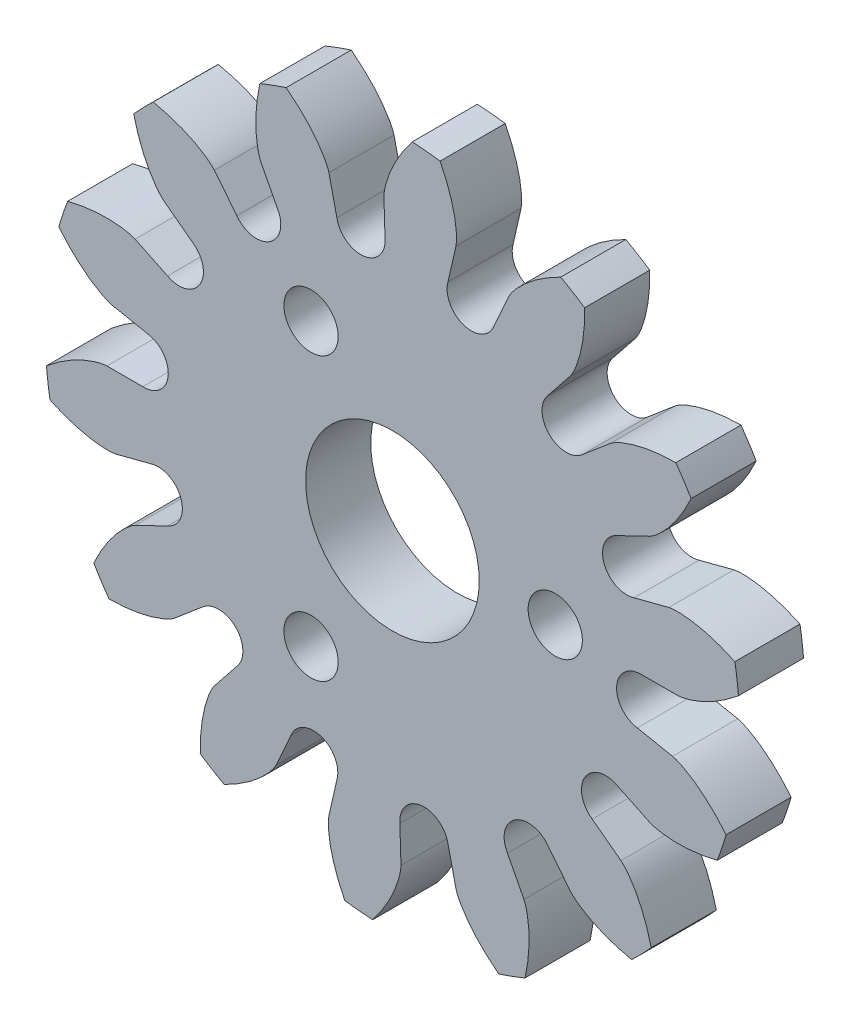
SolidWorks part; units mm, degrees
material "A2017"
ref_plane "正面" through (0, 0, 0) normal (0, 0, 1) x (1, 0, 0)
ref_plane "平面" through (0, 0, 0) normal (0, 1, 0) x (1, 0, 0)
ref_plane "右側面" through (0, 0, 0) normal (1, 0, 0) x (0, 0, -1)
sketch "歯車作図" plane through (0, 0, 0) normal (0, 0, 1) x (1, 0, 0)
  line L0 (0, 0) -> (11.5, 0) construction
  line L1 (11.5, 0) -> (13.1557, 0)
  line L2 (0, 0) -> (15.9243, -1.5543)
  circle A0 centre (0, 0) radius 16
  circle A1 centre (0, 0) radius 14 construction
  circle A2 centre (0, 0) radius 13.1557 construction
  circle A3 centre (0, 0) radius 11.5 construction
  arc A4 (13.9338, -1.36) -> (13.9984, 0.2086) centre (0, 0) ccw
  spline S0 degree 4 poles (13.1557, 0) (13.1962, 0.0018) (13.3095, 0.0121) (13.5229, 0.0532) (13.8623, 0.15) (14.2878, 0.3185) (14.8127, 0.5835) (15.3953, 0.9517) (15.9956, 1.4129) (16.5963, 1.9652) (17.1516, 2.5628) (17.6623, 3.1989) (18.1526, 3.9005) (18.7007, 4.8078) (19.264, 5.9401) (19.7932, 7.3107) (20.2281, 8.8843) (20.5168, 10.4909) (20.6662, 12.1159) (20.6828, 13.7479) (20.5733, 15.3756) (20.3435, 16.9914) (20.0435, 18.386) (19.7179, 19.5668) (19.4366, 20.4368) (19.2304, 21.0178) (19.0543, 21.4853) (18.8956, 21.8825) (18.7682, 22.1927) (18.6164, 22.5421) (18.4593, 22.8947) (18.2968, 23.2444) (18.0021, 23.8548) (17.7431, 24.3427) (17.4714, 24.849) (17.3291, 25.0891) (17.2373, 25.2512) knots 0 0 0 0 0 0.005604 0.015718 0.02996 0.048734 0.068727 0.096889 0.125051 0.153212 0.181374 0.209535 0.237696 0.271429 0.327752 0.384075 0.440398 0.496721 0.553044 0.609367 0.66569 0.722013 0.778336 0.806497 0.834659 0.84874 0.86282 0.876901 0.890982 0.900036 0.909091 0.931818 0.954545 0.977273 1 1 1 1 1 construction
  spline S1 degree 4 poles (13.1557, 0) (13.1962, 0.0018) (13.3095, 0.0121) (13.5229, 0.0532) (13.8623, 0.15) (14.2878, 0.3185) (14.8127, 0.5835) (15.3953, 0.9517) (15.9956, 1.4129) (16.5963, 1.9652) (17.1516, 2.5628) (17.6623, 3.1989) (18.1526, 3.9005) (18.7007, 4.8078) (19.264, 5.9401) (19.7932, 7.3107) (20.2281, 8.8843) (20.5168, 10.4909) (20.6662, 12.1159) (20.6828, 13.7479) (20.5733, 15.3756) (20.3435, 16.9914) (20.0435, 18.386) (19.7179, 19.5668) (19.4366, 20.4368) (19.2304, 21.0178) (19.0543, 21.4853) (18.8956, 21.8825) (18.7682, 22.1927) (18.6164, 22.5421) (18.5243, 22.7488) (18.475, 22.8577) (18.4502, 22.9118) knots 0 0 0 0 0 0.005604 0.015718 0.02996 0.048734 0.068727 0.096889 0.125051 0.153212 0.181374 0.209535 0.237696 0.271429 0.327752 0.384075 0.440398 0.496721 0.553044 0.609367 0.66569 0.722013 0.778336 0.806497 0.834659 0.84874 0.86282 0.876901 0.890982 0.900036 0.909091 0.909091 0.909091 0.909091 0.909091
  dimension "歯先円直径" = 32
  dimension "基礎ピッチ円直径" = 28
  dimension "基礎円直径" = 26.3114
  dimension "全歯丈" = 4.5
  dimension "基準ピッチ" = 1.5708
sketch "ｽｹｯﾁ1" plane through (0, 0, 0) normal (0, 0, 1) x (1, 0, 0)
  circle A0 centre (0, 0) radius 16 construction
  circle A1 centre (0, 0) radius 16
extrude "ﾎﾞｽ - 押し出し1" add sketch "ｽｹｯﾁ1" along normal mid plane 3
sketch "ｽｹｯﾁ3" plane through (0, 0, 1.5) normal (0, 0, 1) x (1, 0, 0)
  line L0 (11.5, 0) -> (13.1557, 0) construction
  line L1 (0, 0) -> (15.9243, -1.5543) construction
  line L2 (11.5, 0) -> (13.1557, 0)
  line L3 (11.4456, -1.1172) -> (15.9243, -1.5543)
  arc A0 (11.4456, -1.1172) -> (11.5, 0) centre (0, 0) ccw
  circle A1 centre (0, 0) radius 16
  arc A2 (15.9243, -1.5543) -> (15.9399, 1.3859) centre (0, 0) ccw
  spline S0 degree 4 poles (3.878, 2999.7691) (4.1335, 73.9467) (7.9689, 1.3767) (11.1984, -0.6096) (13.8623, 0.15) (14.2878, 0.3185) (14.8127, 0.5835) (15.3953, 0.9517) (15.9956, 1.4129) (16.5963, 1.9652) (17.1516, 2.5628) (17.6623, 3.1989) (18.1526, 3.9005) (18.7007, 4.8078) (19.264, 5.9401) (19.7932, 7.3107) (20.2281, 8.8843) (20.5168, 10.4909) (20.6662, 12.1159) (20.6828, 13.7479) (20.5733, 15.3756) (20.3435, 16.9914) (20.0435, 18.386) (19.7179, 19.5668) (19.4366, 20.4368) (19.2304, 21.0178) (19.0543, 21.4853) (18.8956, 21.8825) (18.7682, 22.1927) (17.4635, 25.1948) (18.1341, 22.9305) (4.6054, 50.9334) (-1231.5015, 2749.6934) knots -0.333742 -0.333742 -0.333742 -0.333742 -0.333742 0.005604 0.015718 0.02996 0.048734 0.068727 0.096889 0.125051 0.153212 0.181374 0.209535 0.237696 0.271429 0.327752 0.384075 0.440398 0.496721 0.553044 0.609367 0.66569 0.722013 0.778336 0.806497 0.834659 0.84874 0.86282 0.876901 0.890982 0.900036 1.260415 1.260415 1.260415 1.260415 1.260415 only from (13.1557, 0) to (18.4502, 22.9118) construction
  spline S1 degree 4 poles (13.1557, 0) (13.1962, 0.0018) (13.3095, 0.0121) (13.5229, 0.0532) (13.8623, 0.15) (14.2878, 0.3185) (14.8127, 0.5835) (15.2963, 0.8892) (15.6468, 1.1478) (15.873, 1.3305) (15.9399, 1.3859) knots 0 0 0 0 0 0.005604 0.015718 0.02996 0.048734 0.068727 0.096889 0.108898 0.108898 0.108898 0.108898 0.108898
  dimension "D1" = 0
extrude "ｶｯﾄ - 押し出し1" cut sketch "ｽｹｯﾁ3" against normal through all
pattern_circular "円形ﾊﾟﾀｰﾝ4" count 14 over 360 about axis through (0, 0, 1.5) along (0, 0, -1) of "ｶｯﾄ - 押し出し1"
mirror "ﾐﾗｰ1" about plane through (11.4456, -1.1172, -1.5) normal (-0.0971, -0.9953, 0) of "円形ﾊﾟﾀｰﾝ4", "ｶｯﾄ - 押し出し1"
sketch "ｽｹｯﾁ5" plane through (0, 0, 1.5) normal (0, 0, 1) x (1, 0, 0)
  circle A0 centre (0, 0) radius 4
  dimension "D1" = 8
extrude "ｶｯﾄ - 押し出し3" cut sketch "ｽｹｯﾁ5" against normal through all
hole_wizard "M3 ねじ穴1" positions "ｽｹｯﾁ6" profile "ｽｹｯﾁ7" tap size "M3" standard "JIS" end condition through all
sketch "ｽｹｯﾁ6" plane through (0, 0, 1.5) normal (0, 0, 1) x (1, 0, 0)
  line L0 (7.5, 0) -> (0, 0) construction
  circle A0 centre (0, 0) radius 7.5
  point P0 (7.5, 0)
  dimension "D1" = 15
sketch "ｽｹｯﾁ7" plane through (7.5, 0, 1.5) normal (1, 0, 0) x (0, -1, 0)
  line L0 (0, 0) -> (0, 3)
  line L1 (0, 3) -> (1.25, 3)
  line L2 (1.25, 3) -> (1.25, 0)
  line L5 (1.25, 0) -> (0, 0)
  line L11 (0, -6.35) -> (0, 107.95) construction
  dimension "次ｻｰﾌｪｽまでのねじ下穴ﾄﾞﾘﾙ直径" = 2.5
  dimension "次ｻｰﾌｪｽまでのねじ下穴ﾄﾞﾘﾙの深さ" = 3
cosmetic thread "穴のねじ山1" parameters "D2"=3
pattern_circular "円形ﾊﾟﾀｰﾝ6" count 3 over 360 about axis through (0, 0, -1.5) along (0, 0, 1) of "M3 ねじ穴1"
sketch "ｽｹｯﾁ8" plane through (0, 0, 1.5) normal (0, 0, 1) x (1, 0, 0)
  circle A0 centre (3.6361, 10.91) radius 1.1185
  arc A1 (4.6787, 10.5052) -> (2.559, 11.2117) centre (0, 0) ccw construction
  circle A2 centre (8.0097, 8.252) radius 1.1185
  circle A3 centre (10.7969, 3.9595) radius 1.1185
  circle A4 centre (11.4456, -1.1172) radius 1.1185
  circle A5 centre (9.8274, -5.9726) radius 1.1185
  circle A6 centre (6.2628, -9.6451) radius 1.1185
  circle A7 centre (1.4577, -11.4072) radius 1.1185
  circle A8 centre (-3.6361, -10.91) radius 1.1185
  circle A9 centre (-8.0097, -8.252) radius 1.1185
  circle A10 centre (-10.7969, -3.9595) radius 1.1185
  circle A11 centre (-11.4456, 1.1172) radius 1.1185
  circle A12 centre (-9.8274, 5.9726) radius 1.1185
  circle A13 centre (-6.2628, 9.6451) radius 1.1185
  circle A14 centre (-1.4577, 11.4072) radius 1.1185
  point P34 (0, 0)
  dimension "D1" = 14
extrude "ｶｯﾄ - 押し出し4" cut sketch "ｽｹｯﾁ8" against normal through all
equation "\"モジュール\"= 2"
equation "\"歯数\"= 14"
equation "\"圧力角\"= 20"
equation "\"歯先円直径@歯車作図\" =  ( \"歯数\" + 2 )  * \"モジュール\""
equation "\"基礎ピッチ円直径@歯車作図\" = \"モジュール\" * \"歯数\""
equation "\"基礎円直径@歯車作図\" = \"歯数\" * \"モジュール\" * cos ( \"圧力角\" ) "
equation "\"全歯丈@歯車作図\" = 2.25 * \"モジュール\""
equation "\"基準ピッチ@歯車作図\" = PI * \"モジュール\" / 4"
equation "\"D1@円形ﾊﾟﾀｰﾝ4\"=\"歯数\""
